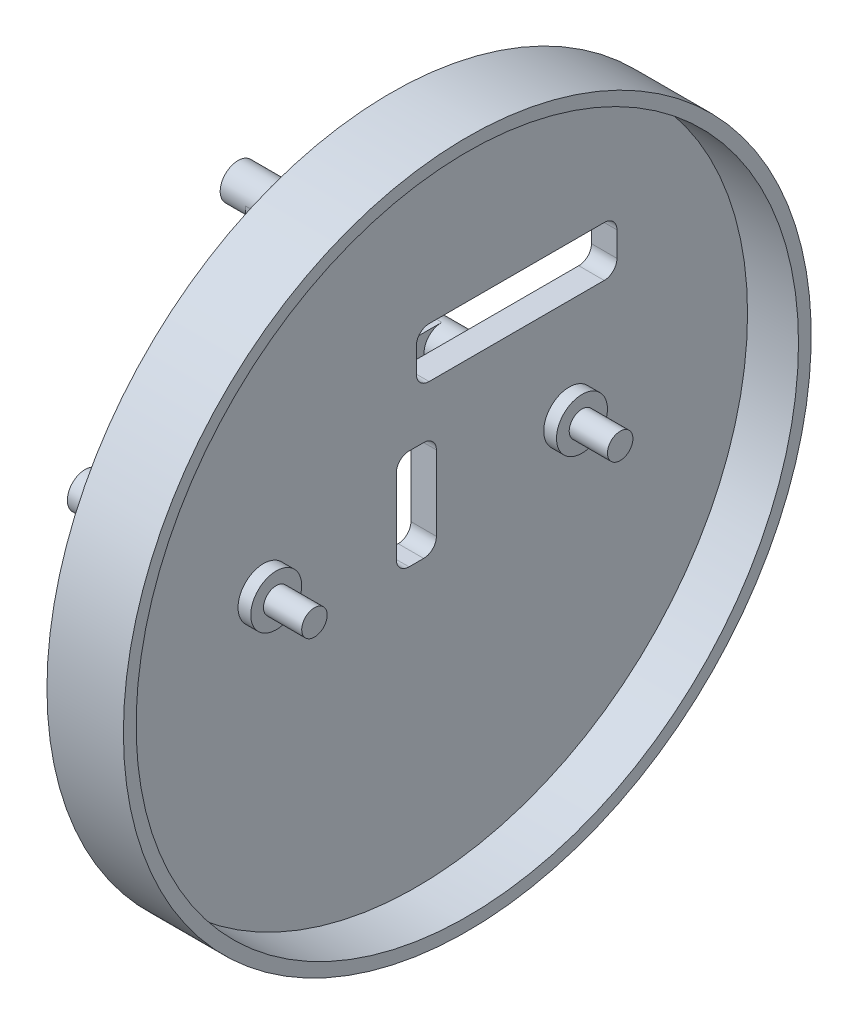
SolidWorks part; units mm, degrees
ref_plane "Front Plane" through (0, 0, 0) normal (0, 0, 1) x (1, 0, 0)
ref_plane "Top Plane" through (0, 0, 0) normal (0, 1, 0) x (1, 0, 0)
ref_plane "Right Plane" through (0, 0, 0) normal (1, 0, 0) x (0, 0, -1)
sketch "Sketch2" plane through (0, 0, 0) normal (1, 0, 0) x (0, 0, -1)
  line L0 (0, -1.778) -> (30.48, -1.778)
  line L1 (0, 1.778) -> (30.48, 1.778)
  arc A0 (0, 1.778) -> (0, -1.778) centre (0, 0) ccw
  arc A1 (30.48, -1.778) -> (30.48, 1.778) centre (30.48, 0) ccw
  dimension "D1" = 3.556
  dimension "D2" = 3.556
  dimension "D3" = 30.48
extrude "Boss-Extrude1" add sketch "Sketch2" along normal blind 2.54
sketch "Sketch3" plane through (0, 0, 0) normal (-1, 0, 0) x (0, 0, 1)
  circle A0 centre (-30.48, 0) radius 1.778
  circle A1 centre (0, 0) radius 1.778
extrude "Boss-Extrude2" add sketch "Sketch3" along normal blind 2.54 and the other way blind 12.7
ref_plane "Plane4" through (12.7, 0, 0) normal (1, 0, 0) x (0, 0, -1)
sketch "Sketch4" plane through (12.7, 0, 0) normal (1, 0, 0) x (0, 0, -1)
  line L0 (30.48, 0) -> (0, 0) construction
  circle A0 centre (15.24, 0) radius 34.29
  point P2 (30.48, 0)
  point P4 (0, 0)
  point P10 (15.24, 0)
  dimension "D1" = 68.58
extrude "Boss-Extrude3" add sketch "Sketch4" along normal blind 7.62
sketch "Sketch5" plane through (0, 0, 0) normal (1, 0, 0) x (0, 0, -1)
  line L0 (30.48, 1.778) -> (0, 1.778) construction
  line L1 (0, -1.778) -> (30.48, -1.778) construction
  line L2 (13.462, -19.05) -> (13.462, 19.05)
  line L3 (17.018, 19.05) -> (17.018, -19.05)
  arc A0 (13.462, -19.05) -> (17.018, -19.05) centre (15.24, -19.05) ccw
  arc A1 (17.018, 19.05) -> (13.462, 19.05) centre (15.24, 19.05) ccw
  point P6 (15.24, 1.778)
  dimension "D1" = 3.556
  dimension "D2" = 3.556
  dimension "D3" = 38.1
  dimension "D4" = 17.272
  dimension "D5" = 17.272
extrude "Boss-Extrude4" add sketch "Sketch5" along normal blind 2.54
sketch "Sketch6" plane through (2.54, 0, 0) normal (1, 0, 0) x (0, 0, -1)
  circle A0 centre (15.24, -19.05) radius 1.778
  circle A1 centre (15.24, 19.05) radius 1.778
extrude "Boss-Extrude5" add sketch "Sketch6" along normal up to surface (10.16 mm away) and the other way blind 5.08 up to face at (12.7, 0, -28.702)
sketch "Sketch7" plane through (20.32, 0, 0) normal (1, 0, 0) x (0, 0, -1)
  circle A0 centre (15.24, 0) radius 33.02
  circle A1 centre (15.24, 0) radius 34.29 construction
  dimension "D1" = 66.04
extrude "Cut-Extrude1" cut sketch "Sketch7" against normal blind 5.08
sketch "Sketch9" plane through (15.24, 0, 0) normal (1, 0, 0) x (0, 0, -1)
  circle A0 centre (0, 0) radius 2.54
  circle A1 centre (30.48, 0) radius 2.54
  circle A3 centre (0, 0) radius 1.778 construction
  circle A4 centre (30.48, 0) radius 1.778 construction
  dimension "D1" = 5.08
  dimension "D2" = 5.08
extrude "Boss-Extrude6" add sketch "Sketch9" along normal blind 1.27
sketch "Sketch10" plane through (16.51, 0, 0) normal (1, 0, 0) x (0, 0, -1)
  circle A0 centre (30.48, 0) radius 1.27
  circle A1 centre (0, 0) radius 1.27
  circle A2 centre (0, 0) radius 2.54 construction
  circle A3 centre (30.48, 0) radius 2.54 construction
  dimension "D1" = 2.54
  dimension "D2" = 2.54
extrude "Boss-Extrude7" add sketch "Sketch10" along normal up to surface (3.81 mm away) up to face at (20.32, 0, -48.26)
sketch "Sketch11" plane through (15.24, 0, 0) normal (1, 0, 0) x (0, 0, -1)
  line L0 (30.48, 0) -> (0, 0) construction
  line L2 (14.51, 5) -> (15.97, 5)
  line L3 (13.24, 3.73) -> (13.24, -3.73)
  line L4 (14.51, -5) -> (15.97, -5)
  line L5 (17.24, 3.73) -> (17.24, -3.73)
  line L6 (13.24, 5) -> (17.24, -5) construction
  line L7 (13.24, -5) -> (17.24, 5) construction
  arc A0 (15.97, -5) -> (17.24, -3.73) centre (15.97, -3.73) ccw
  arc A1 (13.24, -3.73) -> (14.51, -5) centre (14.51, -3.73) ccw
  arc A2 (14.51, 5) -> (13.24, 3.73) centre (14.51, 3.73) ccw
  arc A3 (15.97, 5) -> (17.24, 3.73) centre (15.97, 3.73) cw
  point P4 (15.24, 0)
  dimension "D3" = 1.27
  dimension "D1" = 10
  dimension "D2" = 4
extrude "Cut-Extrude2" cut sketch "Sketch11" against normal up to next
sketch "Sketch15" plane through (15.24, 0, 0) normal (1, 0, 0) x (0, 0, -1)
  line L0 (15.24, -29.9131) -> (15.24, 19.9131) construction
  line L1 (14.51, -5) -> (15.97, -5) construction
  line L3 (15.97, 5) -> (14.51, 5) construction
  line L7 (17.24, -3.73) -> (17.24, 3.73) construction
  line L8 (16.51, 10) -> (33.97, 10)
  line L9 (15.24, 11.27) -> (15.24, 13.73)
  line L10 (16.51, 15) -> (33.97, 15)
  line L11 (35.24, 11.27) -> (35.24, 13.73)
  arc A0 (33.97, 15) -> (35.24, 13.73) centre (33.97, 13.73) cw
  arc A1 (33.97, 10) -> (35.24, 11.27) centre (33.97, 11.27) ccw
  arc A2 (16.51, 10) -> (15.24, 11.27) centre (16.51, 11.27) cw
  arc A3 (15.24, 13.73) -> (16.51, 15) centre (16.51, 13.73) cw
  point P2 (15.24, -5)
  point P7 (15.24, 5)
  point P14 (17.24, 0)
  point P19 (35.24, 10)
  point P22 (15.24, 10)
  point P25 (15.24, 15)
  dimension "D4" = 1.27
  dimension "D1" = 5
  dimension "D2" = 20
  dimension "D3" = 10
extrude "Cut-Extrude3" cut sketch "Sketch15" against normal up to next
